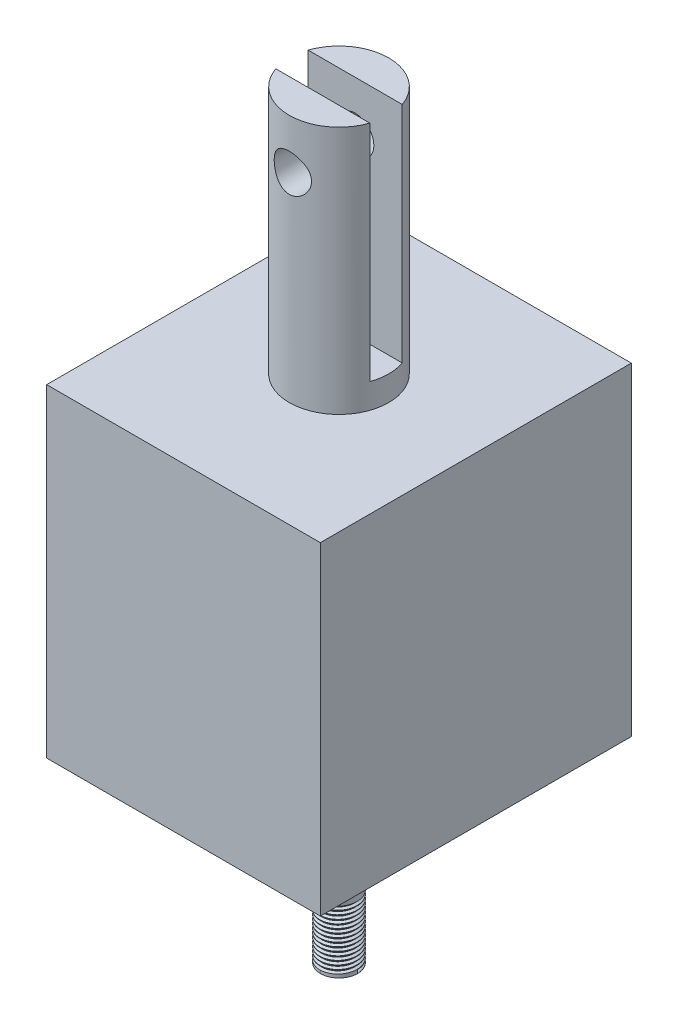
SolidWorks part; units mm, degrees
ref_plane "Front Plane" through (0, 0, 0) normal (0, 0, 1) x (1, 0, 0)
ref_plane "Top Plane" through (0, 0, 0) normal (0, 1, 0) x (1, 0, 0)
ref_plane "Right Plane" through (0, 0, 0) normal (1, 0, 0) x (0, 0, -1)
sketch "Sketch1"
  line L0 (11, 26) -> (11, 0) construction
  line L1 (0, 0) -> (22, 0)
  line L2 (0, 0) -> (0, 26)
  line L3 (0, 26) -> (22, 26)
  line L4 (22, 0) -> (22, 26)
  line L6 (17, 6) -> (5, 6) construction
  line L7 (17, 6) -> (17, 22) construction
  line L8 (17, 22) -> (5, 22) construction
  line L9 (5, 6) -> (5, 22) construction
  circle A0 centre (5, 22) radius 1.5
  circle A1 centre (17, 6) radius 1.5
  point P11 (11, 6)
  dimension "D6" = 3
  dimension "D1" = 22
  dimension "D2" = 26
  dimension "D3" = 12
  dimension "D4" = 16
  dimension "D5" = 6
extrude "Boss-Extrude2" add sketch "Sketch1" along normal blind 25
extrude "Cut-Extrude1" cut sketch "Sketch1<4>" along normal blind 5 contours A1 | A0
sketch "Sketch1<4>" same geometry as "Sketch1"
sketch "Sketch2" plane through (0, 26, 0) normal (0, 1, 0) x (1, 0, 0)
  line L4 (0, -25) -> (22, -25) construction
  line L6 (0, -25) -> (0, 0) construction
  line L8 (22, -13.8) -> (0, -13.8)
  line L9 (22, -13.8) -> (22, -11.2)
  line L10 (22, -11.2) -> (0, -11.2)
  line L11 (0, -13.8) -> (0, -11.2)
  circle A0 centre (11, -12.5) radius 4
  point P6 (11, -13.8)
  point P7 (22, -12.5)
  point P12 (11, -25)
  point P13 (0, -12.5)
  dimension "D1" = 8
  dimension "D2" = 2.6
extrude "Boss-Extrude3" add sketch "Sketch2" along normal blind 20 contours L10 A0 | L8 A0 region at (11, 26, 14.919) region at (11, 26, 10.081)
extrude "Boss-Extrude4" add sketch "Sketch2<3>" along normal blind 2 contours L8 A0 L10 region at (11, 26, 12.5)
sketch "Sketch2<3>" plane through (0, 26, 0) normal (0, 1, 0) x (1, 0, 0) same geometry as "Sketch2"
sketch "Sketch3" plane through (0, 0, 11.2) normal (0, 0, 1) x (1, 0, 0)
  line L0 (14.7829, 46) -> (7.2171, 46) construction
  line L1 (7.2171, 46) -> (11, 46) construction
  line L2 (7.2171, 46) -> (7.2171, 42) construction
  line L3 (7.2171, 42) -> (11, 42) construction
  line L4 (11, 46) -> (11, 42) construction
  circle A0 centre (11, 42) radius 1.5
  dimension "D2" = 3
  dimension "D1" = 4
extrude "Cut-Extrude2" cut sketch "Sketch3" against normal through all both and the other way through all
sketch "Sketch4" plane through (0, 0, 0) normal (0, -1, 0) x (1, 0, 0)
  line L0 (0, 25) -> (22, 0) construction
  line L1 (22, 25) -> (0, 0) construction
  circle A0 centre (11, 12.5) radius 1.5
  dimension "D1" = 3
extrude "Boss-Extrude5" add sketch "Sketch4" along normal blind 15
thread "Thread1" pitch 0.3175 method cut profile "Thread Profile2" start angle 0, offset 0, length 5, pitch 0.3175, diameter 3
ref_plane "Plane2" through (12.5, -15, 12.5) normal (0, 0, 1) x (1, 0, 0)
sketch "Thread Profile2" plane through (12.5, -15, 12.5) normal (0, 0, 1) x (1, 0, 0)
  line L0 (0, 0) -> (0, 0.3175) construction
  line L11 (0, 0) -> (0, 0.2778)
  line L12 (0, 0.2778) -> (-0.1719, 0.1786)
  line L13 (-0.1719, 0.1786) -> (-0.1719, 0.0992)
  line L15 (-0.1719, 0.0992) -> (0, 0)
  line L17 (-0.1719, 0.1389) -> (0, 0.1389) construction
  point P2 (0, 0)
  dimension "Pitch" = 0.3175
  dimension "Profile_Angle" = 60
  dimension "Profile_Land" = 0.0794
  dimension "Profile_Height" = 0.1719
